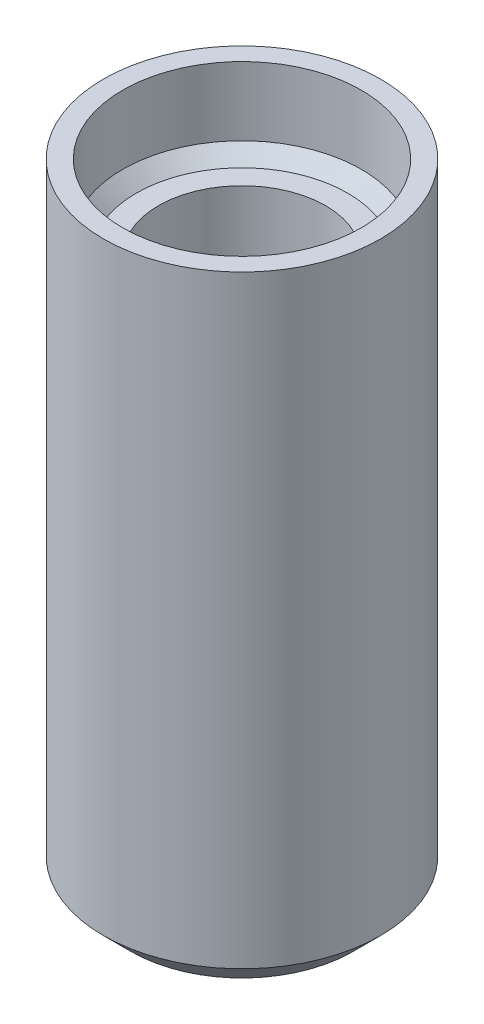
SolidWorks part; units mm, degrees
ref_plane "Front Plane" through (0, 0, 0) normal (0, 0, 1) x (1, 0, 0)
ref_plane "Top Plane" through (0, 0, 0) normal (0, 1, 0) x (1, 0, 0)
ref_plane "Right Plane" through (0, 0, 0) normal (1, 0, 0) x (0, 0, -1)
sketch "Sketch1" plane through (0, 0, 0) normal (0, 1, 0) x (1, 0, 0)
  line L0 (-2.5652, -1.65) -> (2.5652, -1.65)
  circle A0 centre (0, 0) radius 3.05
  circle A1 centre (0, 0) radius 5.05
  dimension "D1" = 6.1
  dimension "D3" = 1.65
  dimension "D2" = 2
extrude "Boss-Extrude1" add sketch "Sketch1" along normal blind 20 contours A1 A0 | L0 A0 region at (0, 0, 2.2227) region at (-4.9072, 0, 0)
sketch "Sketch2" plane through (0, 0, 0) normal (0, -1, 0) x (1, 0, 0)
  circle A1 centre (0, 0) radius 5.05
  circle A2 centre (0, 0) radius 5.05
  dimension "D1" = 0
extrude "Boss-Extrude2" add sketch "Sketch2" against normal blind 2
sketch "Sketch4" plane through (0, 20, 0) normal (0, 1, 0) x (1, 0, 0)
  circle A0 centre (0, 0) radius 4.35
  circle A1 centre (0, 0) radius 5.05
  circle A2 centre (0, 0) radius 5.05
  dimension "D1" = 0
  dimension "D2" = 0.7
extrude "Boss-Extrude3" add sketch "Sketch4" along normal blind 3
chamfer "Chamfer1" distance 1 angle 45 1 edges at (0, 0, 5.05)
chamfer "Chamfer2" distance 0.5 angle 45 1 edges at (0, 20, 4.35)
sketch "Sketch5" plane through (0, 0, 0) normal (0, -1, 0) x (1, 0, 0)
  line L0 (-1.326, 0) -> (1.326, 0) construction
  line L1 (-3.5217, -2) -> (3.5217, -2) construction
  circle A0 centre (0, 0) radius 4.05 construction
  text T0 "<b>7</b>" font "Calibri" height in points 16
  dimension "D1" = 2
extrude "Cut-Extrude1" cut sketch "Sketch5" against normal blind 0.4
extrude "Boss-Extrude4" add sketch "Sketch5<2>" against normal blind 0.4 separate body
sketch "Sketch5<2>" plane through (0, 0, 0) normal (0, -1, 0) x (1, 0, 0) same geometry as "Sketch5"
equation "\"ID\"= 6.3"
equation "\"notch\"= 6.3 / 2 - 1.5"
equation "\"D3@Sketch1\"=\"notch\""
